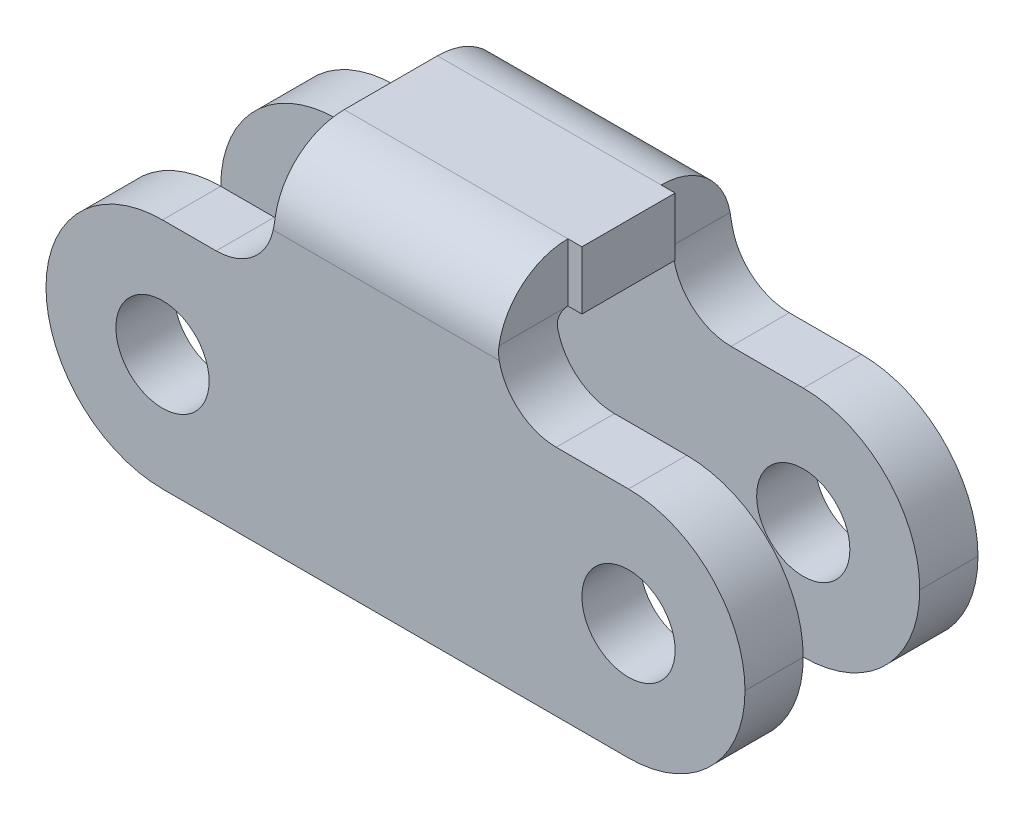
SolidWorks part; units mm, degrees
extrude "Base-Extrude" add sketch "Sketch1" against normal blind 12.7
sketch "Sketch1" plane through (0, 0, 0) normal (0, 0, 1) x (1, 0, 0)
  line L0 (0, 0) -> (43.438, 0) construction
  line L1 (-6.35, -6.35) -> (31.75, -6.35)
  line L2 (-6.35, -6.35) -> (-6.35, 12.7)
  line L3 (31.75, 12.7) -> (-6.35, 12.7)
  line L4 (31.75, 12.7) -> (31.75, -6.35)
  circle A0 centre (0, 0) radius 2.54
  circle A1 centre (25.4, 0) radius 2.54
  dimension "D1" = 5.08
  dimension "D2" = 25.4
  dimension "D3" = 38.1
  dimension "D4" = 19.05
  dimension "D5" = 6.35
  dimension "D6" = 6.35
material "1060 Alloy"
ref_plane "Plane1" through (0, 0, 0) normal (0, 0, 1) x (1, 0, 0)
ref_plane "Plane2" through (0, 0, 0) normal (0, 1, 0) x (-1, 0, 0)
ref_plane "Plane3" through (0, 0, 0) normal (1, 0, 0) x (0, 0, -1)
sketch "Sketch3" plane through (31.75, 0, 0) normal (1, 0, 0) x (0, 0, -1)
  line L0 (3.175, -6.35) -> (3.175, 9.525)
  line L1 (12.7, -6.35) -> (0, -6.35) construction
  line L2 (3.175, 9.525) -> (9.525, 9.525)
  line L3 (9.525, 9.525) -> (9.525, -6.35)
  line L4 (0, 12.7) -> (0, -6.35) construction
  line L5 (12.7, 12.7) -> (0, 12.7) construction
  line L6 (12.7, 12.7) -> (12.7, -6.35) construction
  dimension "D1" = 3.175
extrude "Cut-Extrude1" cut sketch "Sketch3" against normal through all flip side to cut
sketch "Sketch4" plane through (0, 0, 0) normal (0, 0, 1) x (1, 0, 0)
  line L0 (-6.35, 6.35) -> (2.921, 6.35)
  line L1 (-6.35, -6.35) -> (-6.35, 12.7) construction
  line L2 (6.096, 9.525) -> (6.096, 12.7)
  line L3 (31.75, 12.7) -> (-6.35, 12.7) construction
  arc A0 (2.921, 6.35) -> (6.096, 9.525) centre (2.921, 9.525) ccw
  dimension "D3" = 3.175
  dimension "D1" = 6.35
  dimension "D2" = 12.446
extrude "Cut-Extrude2" cut sketch "Sketch4" against normal through all
sketch "Sketch5" plane through (0, 0, 0) normal (0, 0, 1) x (1, 0, 0)
  line L0 (31.75, 6.35) -> (21.463, 6.35)
  line L1 (31.75, 12.7) -> (31.75, -6.35) construction
  line L2 (18.288, 9.525) -> (18.288, 12.7)
  line L3 (31.75, 12.7) -> (6.096, 12.7) construction
  line L4 (-6.35, 6.35) -> (2.921, 6.35) construction
  arc A0 (21.463, 6.35) -> (18.288, 9.525) centre (21.463, 9.525) cw
  arc A1 (2.921, 6.35) -> (6.096, 9.525) centre (2.921, 9.525) ccw construction
  dimension "D1" = 12.192
extrude "Cut-Extrude3" cut sketch "Sketch5" against normal through all flip side to cut
fillet "Fillet1" radius 0.635 2 edges at (12.192, 9.525, -9.525) (12.192, 9.525, -3.175)
fillet "Fillet2" radius 3.81 6 edges at (6.096, 11.1125, -12.7) (6.096, 11.1125, 0) (12.192, 12.7, 0) (12.192, 12.7, -12.7) (18.288, 11.1125, 0) (18.288, 11.1125, -12.7)
fillet "Fillet3" radius 6.35 16 edges at (-6.35, -6.35, -1.5875) (31.75, -6.35, -1.5875) (-6.35, 0, -9.525) (31.75, 0, -3.175) (-6.35, 0, -12.7) (-6.35, 0, -3.175) (-6.35, 6.35, -1.5875) (-6.35, 6.35, -11.1125) (-6.35, 0, 0) (31.75, 0, -9.525) (31.75, 0, -12.7) (31.75, 0, 0) (31.75, 6.35, -11.1125) (-6.35, -6.35, -11.1125) (31.75, 6.35, -1.5875) (31.75, -6.35, -11.1125)
sketch "Sketch6" plane through (18.288, 0, 0) normal (1, 0, 0) x (0, 0, -1)
  line L0 (3.81, 12.7) -> (8.89, 12.7) construction
  line L1 (3.81, 12.7) -> (8.89, 12.7)
  line L2 (3.81, 9.525) -> (8.89, 9.525) construction
  line L3 (3.81, 9.525) -> (8.89, 9.525)
  line L4 (3.81, 12.7) -> (3.81, 9.525)
  line L5 (8.89, 12.7) -> (8.89, 9.525)
extrude "Boss-Extrude1" add sketch "Sketch6" along normal blind 0.762
equation "\"D2@Sketch3\" = \"D1@Sketch3\""
equation "\"D3@Sketch3\" = \"D1@Sketch3\""
